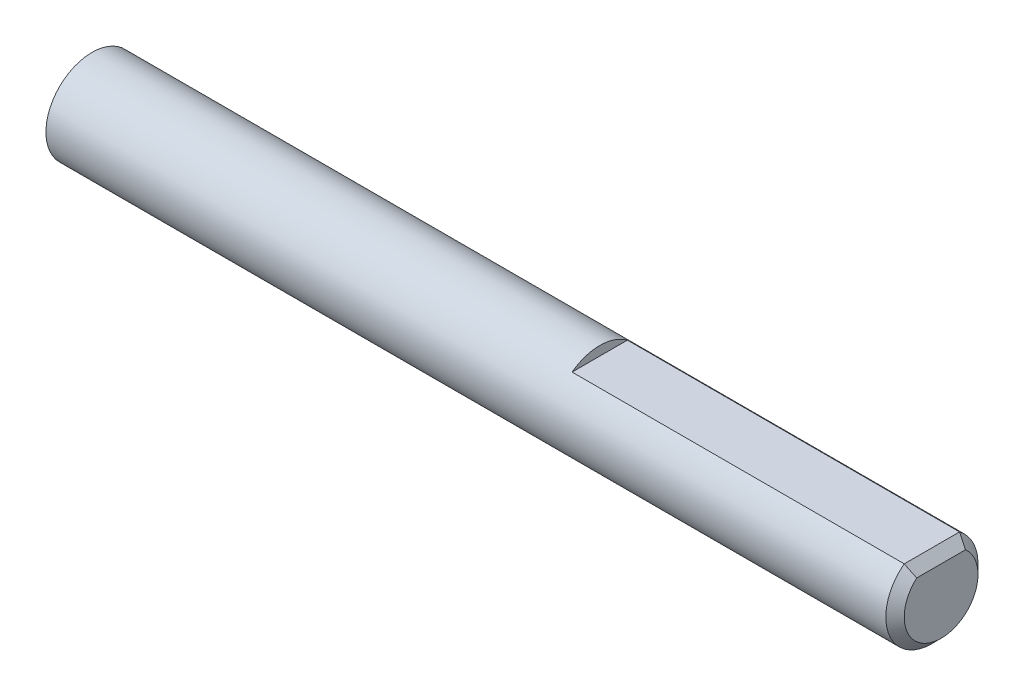
SolidWorks part; units mm, degrees
ref_plane "Front Plane" through (0, 0, 0) normal (0, 0, 1) x (1, 0, 0)
ref_plane "Top Plane" through (0, 0, 0) normal (0, 1, 0) x (1, 0, 0)
ref_plane "Right Plane" through (0, 0, 0) normal (1, 0, 0) x (0, 0, -1)
sketch "Sketch1" plane through (0, 0, 0) normal (1, 0, 0) x (0, 0, -1)
  circle A0 centre (0, 0) radius 2.5
  dimension "D1" = 5
extrude "Boss-Extrude1" add sketch "Sketch1" along normal blind 46.04
ref_plane "Plane1" through (0, 2.5, 0) normal (0, 1, 0) x (1, 0, 0)
sketch "Sketch3" plane through (0, 2.5, 0) normal (0, 1, 0) x (1, 0, 0)
  line L0 (46.04, -2.5) -> (46.04, 2.5) construction
  line L1 (46.04, -1.5) -> (27.53, -1.5)
  line L2 (46.04, -1.5) -> (46.04, 1.5)
  line L3 (46.04, 1.5) -> (27.53, 1.5)
  line L4 (27.53, -1.5) -> (27.53, 1.5)
  line L5 (46.04, 0) -> (0, 0) construction
  dimension "D1" = 3
  dimension "D2" = 18.51
  dimension "D3" = 1.5
extrude "Cut-Extrude1" cut sketch "Sketch3" against normal blind 0.5
chamfer "Chamfer1" distance 0.5 angle 45 2 edges at (46.04, 2, 0) (46.04, -2.5, 0)
